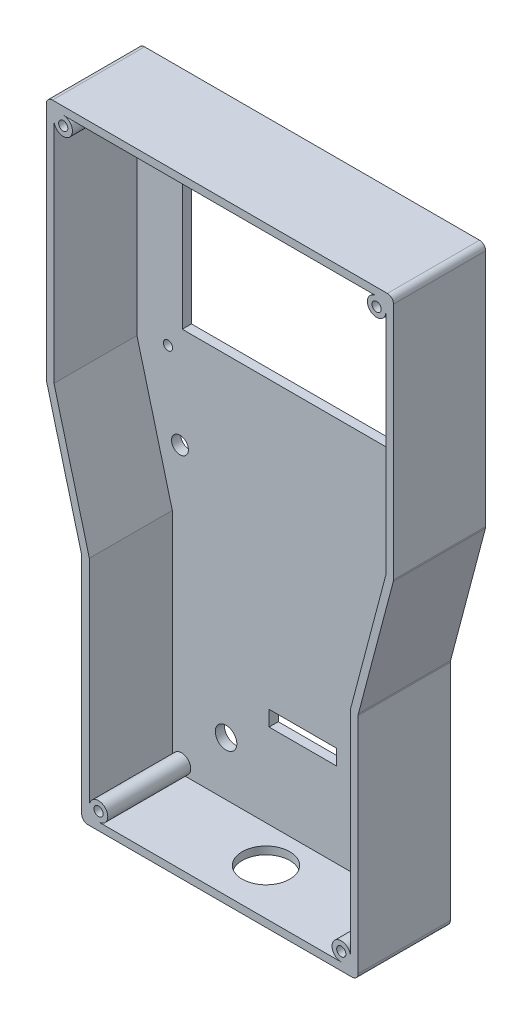
SolidWorks part; units mm, degrees
note: The reader was unsure of these and kept them because the rebuilt part matched: shared geometry of "Sketch1<3>".
ref_plane "Front Plane" through (0, 0, 0) normal (0, 0, 1) x (1, 0, 0)
ref_plane "Top Plane" through (0, 0, 0) normal (0, 1, 0) x (1, 0, 0)
ref_plane "Right Plane" through (0, 0, 0) normal (1, 0, 0) x (0, 0, -1)
sketch "Sketch1" plane through (0, 0, 0) normal (0, 0, 1) x (1, 0, 0)
  line L0 (-39.25, 21.45) -> (-39.25, 25.5)
  line L1 (-39.25, -25.5) -> (39.25, -25.5)
  line L2 (-39.25, -25.5) -> (-39.25, 21.45)
  line L3 (-39.25, 25.5) -> (39.25, 25.5)
  line L4 (39.25, -25.5) -> (39.25, -21.45)
  line L5 (-39.25, -25.5) -> (39.25, 25.5) construction
  line L6 (-39.25, 25.5) -> (39.25, -25.5) construction
  line L11 (0, -907.2464) -> (0, 49092.7536) construction
  line L12 (-46.5, -34.975) -> (46.5, -34.975) construction
  line L13 (-46.5, -34.975) -> (-46.5, 34.975) construction
  line L14 (-46.5, 34.975) -> (46.5, 34.975) construction
  line L15 (46.5, -34.975) -> (46.5, 34.975) construction
  line L16 (-46.5, -34.975) -> (46.5, 34.975) construction
  line L17 (-46.5, 34.975) -> (46.5, -34.975) construction
  line L18 (-1000, 0) -> (49000, 0) construction
  line L19 (-56.5, 44.975) -> (56.5, 44.975)
  line L20 (-28, -118.5) -> (28, -118.5)
  line L21 (-35, -111.5) -> (-35, -45.5)
  line L22 (-28, -38.5) -> (28, -38.5)
  line L23 (35, -111.5) -> (35, -45.5)
  line L24 (-35, -118.5) -> (35, -38.5) construction
  line L25 (-35, -38.5) -> (35, -118.5) construction
  line L26 (11, -118.5) -> (-11, -118.5)
  line L27 (11, -118.5) -> (11, -123.5)
  line L28 (11, -123.5) -> (-11, -123.5)
  line L29 (-11, -118.5) -> (-11, -123.5)
  line L30 (56.5, 44.975) -> (56.5, -34.975)
  line L31 (56.5, -34.975) -> (45, -78.5)
  line L32 (45, -78.5) -> (45, -153.5)
  line L33 (45, -153.5) -> (-45, -153.5)
  line L34 (-45, -78.5) -> (-45, -153.5)
  line L35 (-56.5, -34.975) -> (-45, -78.5)
  line L36 (-56.5, 44.975) -> (-56.5, -34.975)
  line L37 (43.95, 21.45) -> (43.95, -21.45)
  line L38 (39.25, -21.45) -> (43.95, -21.45)
  line L39 (39.25, 21.45) -> (43.95, 21.45)
  line L40 (39.25, -25.5) -> (39.25, -21.45)
  line L41 (39.25, 21.45) -> (39.25, 25.5)
  line L42 (39.25, 21.45) -> (39.25, 25.5)
  circle A0 centre (43.9, 32.375) radius 1.5
  circle A1 centre (-43.9, 32.375) radius 1.5
  circle A2 centre (43.9, -32.375) radius 1.5
  circle A3 centre (-43.9, -32.375) radius 1.5
  circle A4 centre (40, -58.5) radius 2.75
  circle A5 centre (-40, -58.5) radius 2.75
  circle A6 centre (25, -133.5) radius 2.75
  circle A7 centre (-25, -133.5) radius 3.5
  arc A8 (35, -111.5) -> (28, -118.5) centre (28, -111.5) cw
  arc A9 (-28, -118.5) -> (-35, -111.5) centre (-28, -111.5) cw
  arc A10 (-35, -45.5) -> (-28, -38.5) centre (-28, -45.5) cw
  arc A11 (35, -45.5) -> (28, -38.5) centre (28, -45.5) ccw
  point P0 (0, 0)
  point P7 (43.95, 0)
  point P11 (0, 0)
  point P28 (0, -78.5)
  point P41 (0, -123.5)
  point P50 (0, 44.975)
  point P57 (0, -153.5)
  dimension "D7" = 3
  dimension "D8" = 2.6
  dimension "D14" = 5.5
  dimension "D18" = 20
  dimension "D20" = 5.5
  dimension "D21" = 7
  dimension "D28" = 7
  dimension "D29" = 7
  dimension "D30" = 7
  dimension "D31" = 7
  dimension "D1" = 78.5
  dimension "D2" = 51
  dimension "D3" = 42.9
  dimension "D4" = 4.7
  dimension "D5" = 93
  dimension "D6" = 69.95
  dimension "D9" = 2.6
  dimension "D10" = 13
  dimension "D11" = 70
  dimension "D12" = 80
  dimension "D13" = 5
  dimension "D15" = 20
  dimension "D16" = 22
  dimension "D17" = 5
  dimension "D19" = 20
  dimension "D22" = 15
  dimension "D23" = 10
  dimension "D24" = 10
  dimension "D25" = 35
  dimension "D26" = 10
  dimension "D27" = 43.95
extrude "Boss-Extrude1" add sketch "Sketch1" along normal blind 30
sketch "Sketch2" plane through (0, 0, 30) normal (0, 0, 1) x (1, 0, 0)
  line L0 (56.5, 44.975) -> (56.5, -34.975) construction
  line L1 (56.5, -34.975) -> (45, -78.5) construction
  line L2 (45, -78.5) -> (45, -153.5) construction
  line L3 (45, -153.5) -> (-45, -153.5) construction
  line L4 (-45, -78.5) -> (-45, -153.5) construction
  line L5 (-56.5, -34.975) -> (-45, -78.5) construction
  line L6 (-56.5, 44.975) -> (-56.5, -34.975) construction
  line L7 (-56.5, 44.975) -> (56.5, 44.975) construction
  line L8 (56.5, 44.975) -> (56.5, -34.975)
  line L9 (56.5, -34.975) -> (45, -78.5)
  line L10 (45, -78.5) -> (45, -153.5)
  line L11 (45, -153.5) -> (-45, -153.5)
  line L12 (-45, -78.5) -> (-45, -153.5)
  line L13 (-56.5, -34.975) -> (-45, -78.5)
  line L14 (-56.5, 44.975) -> (-56.5, -34.975)
  line L15 (-56.5, 44.975) -> (56.5, 44.975)
  line L16 (54, 42.475) -> (54, -34.6503)
  line L17 (54, -34.6503) -> (42.5, -78.1753)
  line L18 (42.5, -78.1753) -> (42.5, -151)
  line L19 (42.5, -151) -> (-42.5, -151)
  line L20 (-42.5, -78.1753) -> (-42.5, -151)
  line L21 (-54, -34.6503) -> (-42.5, -78.1753)
  line L22 (-54, 42.475) -> (-54, -34.6503)
  line L23 (-54, 42.475) -> (54, 42.475)
  dimension "D1" = 2.5
extrude "Cut-Extrude2" cut sketch "Sketch2" against normal offset from surface (27 mm away) 3 up to face at (0, -121, 0)
extrude "Cut-Extrude4" cut sketch "Sketch1<3>" along normal blind 1 contours L23 A11 L22 A10 L21 A9 L20 A8
sketch "Sketch1<3>" plane through (0, 0, 0) normal (0, 0, 1) x (1, 0, 0) same geometry as "Sketch1"
fillet "Fillet1" radius 2 8 edges at (56.5, -34.975, 15) (45, -78.5, 15) (45, -153.5, 15) (-45, -153.5, 15) (-45, -78.5, 15) (-56.5, -34.975, 15) (-56.5, 44.975, 15) (56.5, 44.975, 15)
sketch "Sketch5" plane through (0, 0, 3) normal (0, 0, 1) x (1, 0, 0)
  line L0 (0, -974.5) -> (0, 49025.5) construction
  line L1 (39.25, 25.5) -> (-39.25, 25.5) construction
  line L2 (-54, 42.475) -> (54, 42.475) construction
  line L3 (54, 42.475) -> (54, -34.6503) construction
  line L4 (-42.5, -151) -> (42.5, -151) construction
  line L5 (42.5, -78.1753) -> (42.5, -151) construction
  line L6 (-42.5, -151) -> (-42.5, -148)
  line L7 (39.5, -151) -> (42.5, -151)
  line L8 (-54, 42.475) -> (-51, 42.475)
  line L9 (-54, 39.475) -> (-54, 42.475)
  line L10 (-39.5, -151) -> (-42.5, -151)
  line L14 (54, -34.6503) -> (54, 42.475)
  line L15 (54, 42.475) -> (-54, 42.475)
  line L16 (-54, 42.475) -> (-54, -34.6503)
  line L17 (-54, -34.6503) -> (-42.5, -78.1753)
  line L18 (-42.5, -78.1753) -> (-42.5, -151)
  line L19 (-42.5, -151) -> (42.5, -151)
  line L20 (42.5, -151) -> (42.5, -78.1753)
  line L21 (42.5, -78.1753) -> (54, -34.6503)
  line L22 (54, 39.475) -> (54, 42.475)
  line L23 (54, 42.475) -> (51, 42.475)
  line L28 (42.5, -151) -> (42.5, -148)
  arc A0 (51, 42.475) -> (54, 39.475) centre (51, 39.475) ccw
  arc A1 (42.5, -148) -> (39.5, -151) centre (39.5, -148) ccw
  arc A2 (-42.5, -148) -> (-39.5, -151) centre (-39.5, -148) cw
  arc A3 (-51, 42.475) -> (-54, 39.475) centre (-51, 39.475) cw
  point P5 (0, 25.5)
  dimension "D1" = 6
  dimension "D2" = 0
extrude "Boss-Extrude2" add sketch "Sketch5" along normal through all
sketch "Sketch6" plane through (0, 0, 30) normal (0, 0, 1) x (1, 0, 0)
  line L0 (0, -1000) -> (0, 49000) construction
  circle A0 centre (51, 39.475) radius 1.5
  arc A1 (51, 42.475) -> (54, 39.475) centre (51, 39.475) ccw construction
  circle A2 centre (39.5, -148) radius 1.5
  arc A4 (42.5, -148) -> (39.5, -151) centre (39.5, -148) ccw construction
  circle A5 centre (-39.5, -148) radius 1.5
  circle A6 centre (-51, 39.475) radius 1.5
  dimension "D1" = 3
extrude "Cut-Extrude5" cut sketch "Sketch6" against normal blind 20
sketch "Sketch7" plane through (0, -153.5, 0) normal (0, -1, 0) x (1, 0, 0)
  line L0 (56.4336, 0) -> (56.4336, 30) construction
  circle A0 centre (0, 15) radius 7.75
  point P5 (56.4336, 15)
  dimension "D1" = 15.5
extrude "Cut-Extrude6" cut sketch "Sketch7" against normal up to next
